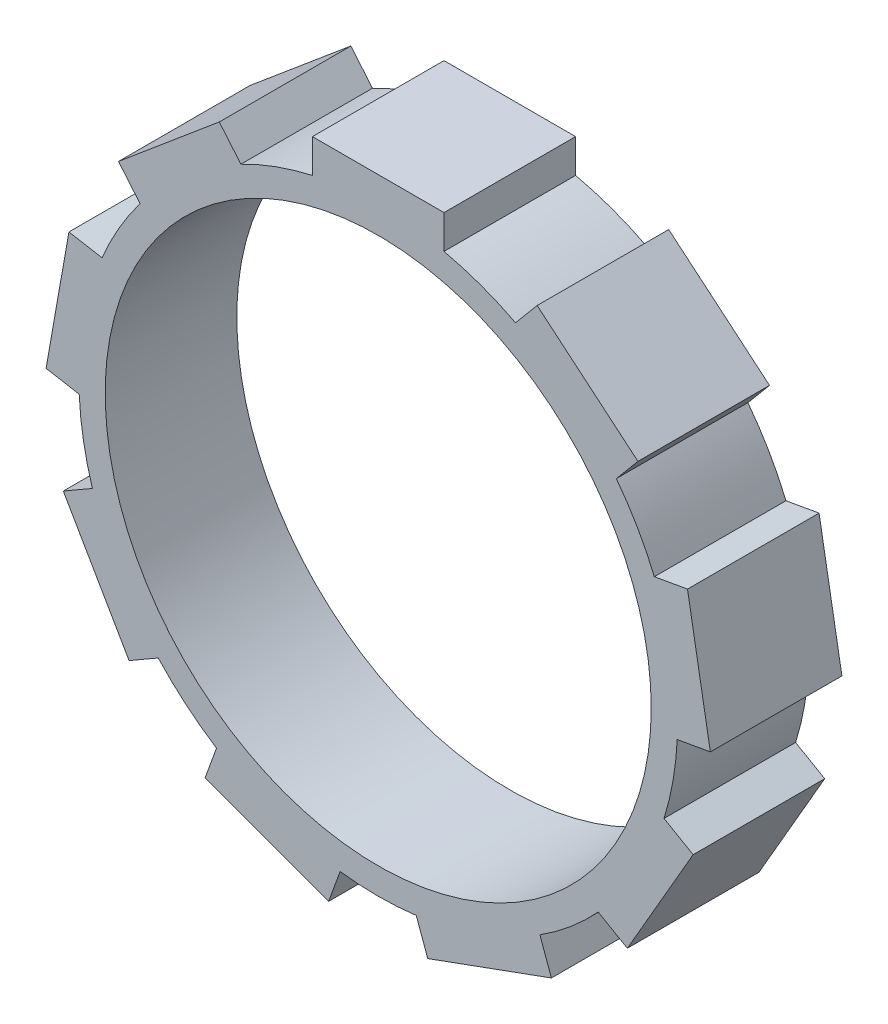
SolidWorks part; units mm, degrees
ref_plane "Alzado" through (0, 0, 0) normal (0, 0, 1) x (1, 0, 0)
ref_plane "Planta" through (0, 0, 0) normal (0, 1, 0) x (1, 0, 0)
ref_plane "Vista lateral" through (0, 0, 0) normal (1, 0, 0) x (0, 0, -1)
sketch "Croquis1" plane through (0, 0, 0) normal (0, 0, 1) x (1, 0, 0)
  line L0 (12.0788, 22.1735) -> (19.7392, 15.7457)
  line L1 (-5, 24.75) -> (5, 24.75)
  line L2 (-5, 24.75) -> (-5, 22.1937)
  line L4 (5, 24.75) -> (5, 22.1937)
  line L5 (-5, 24.75) -> (5, 20.75) construction
  line L6 (-5, 20.75) -> (5, 24.75) construction
  line L7 (12.0788, 22.1735) -> (10.4356, 20.2153)
  line L8 (19.7392, 15.7457) -> (18.0961, 13.7875)
  line L9 (23.5058, 9.2218) -> (25.2422, -0.6262)
  line L10 (23.5058, 9.2218) -> (20.9883, 8.7779)
  line L11 (25.2422, -0.6262) -> (22.7248, -1.0701)
  line L12 (23.9341, -8.0449) -> (18.9341, -16.7051)
  line L13 (23.9341, -8.0449) -> (21.7204, -6.7667)
  line L14 (18.9341, -16.7051) -> (16.7204, -15.427)
  line L15 (13.1635, -21.5473) -> (3.7665, -24.9675)
  line L16 (13.1635, -21.5473) -> (12.2892, -19.1452)
  line L17 (3.7665, -24.9675) -> (2.8922, -22.5654)
  line L18 (-3.7665, -24.9675) -> (-13.1635, -21.5473)
  line L19 (-3.7665, -24.9675) -> (-2.8922, -22.5654)
  line L20 (-13.1635, -21.5473) -> (-12.2892, -19.1452)
  line L21 (-18.9341, -16.7051) -> (-23.9341, -8.0449)
  line L22 (-18.9341, -16.7051) -> (-16.7204, -15.427)
  line L23 (-23.9341, -8.0449) -> (-21.7204, -6.7667)
  line L24 (-25.2422, -0.6262) -> (-23.5058, 9.2218)
  line L25 (-25.2422, -0.6262) -> (-22.7248, -1.0701)
  line L26 (-23.5058, 9.2218) -> (-20.9883, 8.7779)
  line L27 (-19.7392, 15.7457) -> (-12.0788, 22.1735)
  line L28 (-19.7392, 15.7457) -> (-18.0961, 13.7875)
  line L29 (-12.0788, 22.1735) -> (-10.4356, 20.2153)
  circle A0 centre (0, 0) radius 20.75
  arc A1 (-5, 22.1937) -> (5, 22.1937) centre (0, 0) ccw
  point P4 (0, 22.75)
  point P45 (0, 0)
  dimension "D1" = 41.5
  dimension "D2" = 2
  dimension "D3" = 10
  dimension "D4" = 9
extrude "Saliente-Extruir1" add sketch "Croquis1" along normal blind 10 contours A1 L4 L1 L2 A0 | A1 L29 L27 L28 | A1 L8 L0 L7 | A1 L26 L24 L25 | A1 L11 L9 L10 | A1 L14 L12 L13 | A1 L23 L21 L22 | A1 L20 L18 L19 | A1 L17 L15 L16 region at (15.2029, 18.1181, 0) region at (14.2006, 16.9236, 0) region at (23.2922, 4.107, 0) region at (20.4828, -11.8257, 0) region at (-15.2029, 18.1181, 0) region at (8.0893, -22.2251, 0) region at (-23.2922, 4.107, 0) region at (-8.0893, -22.2251, 0) region at (-20.4828, -11.8257, 0)
